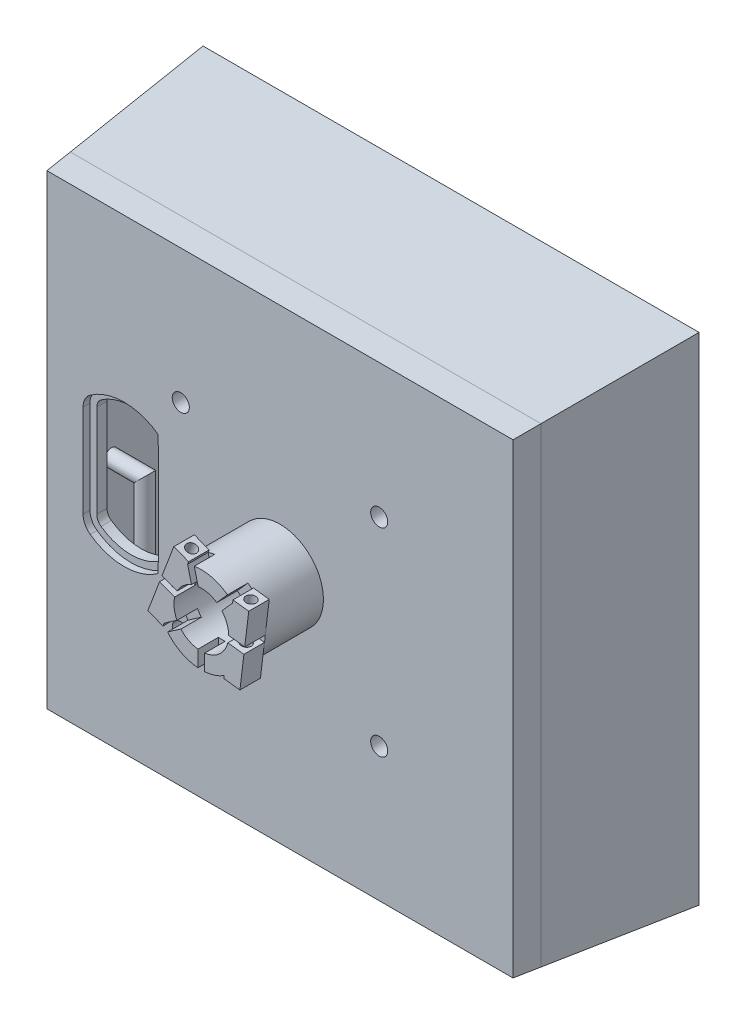
SolidWorks part; units mm, degrees
ref_plane "Front Plane" through (0, 0, 0) normal (1, 0, 0) x (0, 1, 0)
ref_plane "Top Plane" through (0, 0, 0) normal (0, 0, 1) x (0, 1, 0)
ref_plane "Right Plane" through (0, 0, 0) normal (0, 1, 0) x (-1, 0, 0)
sketch "Sketch1" plane through (0, 0, 0) normal (0, 0, 1) x (0, 1, 0)
  line L1 (0, 0) -> (100, 0)
  line L2 (0, 0) -> (0, -100)
  line L3 (0, -100) -> (100, -100)
  line L4 (100, 0) -> (100, -100)
  dimension "D1" = 100
  dimension "D2" = 100
sketch "Sketch11" plane through (0, 0, 0) normal (0, 0, 1) x (0, 1, 0)
  line L1 (0, 0) -> (145, 0)
  line L2 (0, 0) -> (0, -145)
  line L3 (0, -145) -> (145, -145)
  line L4 (145, 0) -> (145, -145)
  dimension "D1" = 145
extrude "Boss-Extrude5" add sketch "Sketch11" along normal blind 50
chamfer "Chamfer1" distance 50 angle 5 4 edges at (0, 72.5, 50) (72.5, 145, 50) (145, 72.5, 50) (72.5, 0, 50) first distance on face at (0, 72.5, 25) first distance on face at (72.5, 145, 25) first distance on face at (145, 72.5, 25) first distance on face at (72.5, 0, 25)
shell "Shell1" thickness 5
sketch "Sketch3" plane through (0, 0, 50) normal (0, 0, 1) x (1, 0, 0)
  line L0 (17.5, 72.5) -> (127.5, 72.5) construction
  line L1 (43.94, 36.94) -> (101.06, 36.94) construction
  line L2 (36.94, 43.94) -> (36.94, 101.06) construction
  line L3 (43.94, 108.06) -> (101.06, 108.06) construction
  line L4 (108.06, 43.94) -> (108.06, 101.06) construction
  line L5 (36.94, 36.94) -> (108.06, 108.06) construction
  line L6 (36.94, 108.06) -> (108.06, 36.94) construction
  line L9 (72.5, 7.5) -> (72.5, 92.5) construction
  line L12 (140.6256, 140.6256) -> (4.3744, 140.6256) construction
  line L13 (4.3744, 140.6256) -> (4.3744, 4.3744) construction
  circle A0 centre (72.5, 72.5) radius 12.7
  circle A1 centre (43.5, 101.5) radius 2.5
  circle A2 centre (101.5, 43.5) radius 2.5
  circle A3 centre (101.5, 101.5) radius 2.5
  circle A4 centre (43.5, 43.5) radius 2.5
  arc A5 (43.94, 36.94) -> (36.94, 43.94) centre (43.94, 43.94) cw construction
  arc A6 (101.06, 36.94) -> (108.06, 43.94) centre (101.06, 43.94) ccw construction
  arc A7 (108.06, 101.06) -> (101.06, 108.06) centre (101.06, 101.06) ccw construction
  arc A8 (43.94, 108.06) -> (36.94, 101.06) centre (43.94, 101.06) ccw construction
  point P17 (72.5, 140.6256)
  point P22 (4.3744, 72.5)
  point P30 (72.5, 72.5)
  dimension "D1" = 25.4
  dimension "D3" = 5
  dimension "D5" = 7
  dimension "D2" = 71.12
  dimension "D4" = 58
extrude "Cut-Extrude3" cut sketch "Sketch3" against normal up to surface (5 mm away) up to face at (72.5, 72.5, 45)
sketch "Sketch5" plane through (0, 0, 45) normal (0, 0, -1) x (1, 0, 0)
  circle A2 centre (72.5, -72.5) radius 12.7
  circle A3 centre (72.5, -72.5) radius 8
  circle A4 centre (72.5, -72.5) radius 12.7 construction
  dimension "D1" = 16
extrude "Boss-Extrude6" add sketch "Sketch5" against normal blind 28
sketch "Sketch12" plane through (0, 0, 73) normal (0, 0, 1) x (1, 0, 0)
  line L1 (58.8041, 72.6436) -> (60, 60) construction
  line L2 (60, 60) -> (60.7967, 72.675) construction
  arc A0 (31.0257, 37.6808) -> (31.2752, 37.6216) centre (31.2752, 38.1766) ccw
  arc A1 (31.0257, 37.6808) -> (30.5229, 38.269) centre (31.4752, 38.5741) cw
  arc A2 (30.5229, 38.269) -> (30.3584, 38.3716) centre (30.38, 38.2232) ccw
  arc A3 (30.3584, 38.3716) -> (30.2795, 38.3596) centre (31.2752, 32.073) ccw
  arc A4 (32.1919, 38.3716) -> (32.2709, 38.3596) centre (31.2752, 32.073) cw
  arc A5 (32.0275, 38.269) -> (32.1919, 38.3716) centre (32.1703, 38.2232) cw
  arc A6 (31.5246, 37.6808) -> (32.0275, 38.269) centre (31.0752, 38.5741) ccw
  arc A7 (31.5246, 37.6808) -> (31.2752, 37.6216) centre (31.2752, 38.1766) cw
  arc A8 (59.3046, 72.2263) -> (59.8122, 71.9146) centre (59.8034, 72.4695) ccw
  arc A9 (59.3046, 72.2263) -> (59.2119, 72.5345) centre (60.2034, 72.6645) cw
  arc A10 (59.2119, 72.5345) -> (59.052, 72.6646) centre (59.0632, 72.515) ccw
  arc A11 (59.052, 72.6646) -> (58.8041, 72.6436) centre (60, 60) ccw
  arc A12 (60.5483, 72.6882) -> (60.7967, 72.675) centre (60, 60) cw
  arc A13 (60.3926, 72.5531) -> (60.5483, 72.6882) centre (60.5419, 72.5383) cw
  arc A14 (60.3097, 72.2421) -> (60.3926, 72.5531) centre (59.3975, 72.6518) ccw
  arc A15 (60.3097, 72.2421) -> (59.8122, 71.9146) centre (59.8034, 72.4695) cw
  arc A16 (61.2257, 72.1846) -> (61.6783, 71.7973) centre (61.7565, 72.3467) ccw
  circle A17 centre (60, 60) radius 12.7 construction
  arc A18 (61.2257, 72.1846) -> (61.1824, 72.5035) centre (62.1821, 72.4768) cw
  arc A19 (61.1824, 72.5035) -> (61.0448, 72.6569) centre (61.0325, 72.5075) ccw
  arc A20 (61.0448, 72.6569) -> (60.7967, 72.675) centre (60, 60) ccw
  arc A21 (62.5265, 72.4462) -> (62.7697, 72.3943) centre (60, 60) cw
  arc A22 (62.3515, 72.3371) -> (62.5265, 72.4462) centre (62.4966, 72.2992) cw
  arc A23 (62.221, 72.043) -> (62.3515, 72.3371) centre (61.3841, 72.5903) ccw
  arc A24 (62.221, 72.043) -> (61.6783, 71.7973) centre (61.7565, 72.3467) cw
  arc A25 (63.1167, 71.8428) -> (63.5032, 71.3895) centre (63.6663, 71.9199) ccw
  arc A26 (63.1167, 71.8428) -> (63.1239, 72.1645) centre (64.107, 71.9818) cw
  arc A27 (63.1239, 72.1645) -> (63.012, 72.3377) centre (62.9764, 72.1919) ccw
  arc A28 (63.012, 72.3377) -> (62.7697, 72.3943) centre (60, 60) ccw
  arc A29 (64.4424, 71.8977) -> (64.6745, 71.8084) centre (60, 60) cw
  arc A30 (64.2525, 71.8174) -> (64.4424, 71.8977) centre (64.3899, 71.7572) cw
  arc A31 (64.0776, 71.5473) -> (64.2525, 71.8174) centre (63.3366, 72.2188) ccw
  arc A32 (64.0776, 71.5473) -> (63.5032, 71.3895) centre (63.6663, 71.9199) cw
  arc A33 (64.931, 71.2094) -> (65.2417, 70.7012) centre (65.4859, 71.1996) ccw
  arc A34 (64.931, 71.2094) -> (64.9884, 71.5261) centre (65.9308, 71.1918) cw
  arc A35 (64.9884, 71.5261) -> (64.9049, 71.7146) centre (64.847, 71.5762) ccw
  arc A36 (64.9049, 71.7146) -> (64.6745, 71.8084) centre (60, 60) ccw
  arc A37 (66.2489, 71.0563) -> (66.4642, 70.9318) centre (60, 60) cw
  arc A38 (66.0488, 71.0067) -> (66.2489, 71.0563) centre (66.1751, 70.9257) cw
  arc A39 (65.8338, 70.7672) -> (66.0488, 71.0067) centre (65.2069, 71.5464) ccw
  arc A40 (65.8338, 70.7672) -> (65.2417, 70.7012) centre (65.4859, 71.1996) cw
  arc A41 (66.6238, 70.3001) -> (66.8513, 69.7495) centre (67.1704, 70.2036) ccw
  arc A42 (66.6238, 70.3001) -> (66.73, 70.6038) centre (67.6086, 70.1262) cw
  arc A43 (66.73, 70.6038) -> (66.6771, 70.8031) centre (66.5982, 70.6755) ccw
  arc A44 (66.6771, 70.8031) -> (66.4642, 70.9318) centre (60, 60) ccw
  arc A45 (67.9015, 69.9426) -> (68.0947, 69.786) centre (60, 60) cw
  arc A46 (67.6961, 69.9249) -> (67.9015, 69.9426) centre (67.8082, 69.8252) cw
  arc A47 (67.4463, 69.7221) -> (67.6961, 69.9249) centre (66.9491, 70.5897) ccw
  arc A48 (67.4463, 69.7221) -> (66.8513, 69.7495) centre (67.1704, 70.2036) cw
  arc A49 (68.1535, 69.1371) -> (68.2921, 68.5577) centre (68.6783, 68.9563) ccw
  arc A50 (68.1535, 69.1371) -> (68.306, 69.4205) centre (69.099, 68.8113) cw
  arc A51 (68.306, 69.4205) -> (68.2849, 69.6255) centre (68.187, 69.5119) ccw
  arc A52 (68.2849, 69.6255) -> (68.0947, 69.786) centre (60, 60) ccw
  arc A53 (69.3596, 68.5841) -> (69.5259, 68.3992) centre (60, 60) cw
  arc A54 (69.154, 68.5988) -> (69.3596, 68.5841) centre (69.2491, 68.4828) cw
  arc A55 (68.8755, 68.4375) -> (69.154, 68.5988) centre (68.5201, 69.3722) ccw
  arc A56 (68.8755, 68.4375) -> (68.2921, 68.5577) centre (68.6783, 68.9563) cw
  arc A57 (69.4825, 67.7491) -> (69.5287, 67.1552) centre (69.9725, 67.4884) ccw
  arc A58 (69.4825, 67.7491) -> (69.6774, 68.0052) centre (70.3654, 67.2794) cw
  arc A59 (69.6774, 68.0052) -> (69.6886, 68.211) centre (69.5742, 68.114) ccw
  arc A60 (69.6886, 68.211) -> (69.5259, 68.3992) centre (60, 60) ccw
  arc A61 (70.5872, 67.0143) -> (70.7226, 66.8056) centre (60, 60) cw
  arc A62 (70.3864, 67.0609) -> (70.5872, 67.0143) centre (70.4622, 66.9314) cw
  arc A63 (70.0862, 66.9452) -> (70.3864, 67.0609) centre (69.8814, 67.924) ccw
  arc A64 (70.0862, 66.9452) -> (69.5287, 67.1552) centre (69.9725, 67.4884) cw
  arc A65 (70.578, 66.1703) -> (70.5307, 65.5765) centre (71.0212, 65.8362) ccw
  arc A66 (70.578, 66.1703) -> (70.8105, 66.3927) centre (71.3765, 65.5683) cw
  arc A67 (70.8105, 66.3927) -> (70.8538, 66.5943) centre (70.7256, 66.5164) ccw
  arc A68 (70.8538, 66.5943) -> (70.7226, 66.8056) centre (60, 60) ccw
  arc A69 (71.5542, 65.2717) -> (71.6552, 65.0444) centre (60, 60) cw
  arc A70 (71.3631, 65.3492) -> (71.5542, 65.2717) centre (71.4177, 65.2095) cw
  arc A71 (71.0484, 65.2819) -> (71.3631, 65.3492) centre (70.9993, 66.2806) ccw
  arc A72 (71.0484, 65.2819) -> (70.5307, 65.5765) centre (71.0212, 65.8362) cw
  arc A73 (71.413, 64.4395) -> (71.2734, 63.8604) centre (71.7985, 64.0402) ccw
  arc A74 (71.413, 64.4395) -> (71.6775, 64.6229) centre (72.1075, 63.7201) cw
  arc A75 (71.6775, 64.6229) -> (71.7518, 64.8152) centre (71.613, 64.7583) ccw
  arc A76 (71.7518, 64.8152) -> (71.6552, 65.0444) centre (60, 60) ccw
  arc A77 (72.2366, 63.3994) -> (72.3008, 63.159) centre (60, 60) cw
  arc A78 (72.06, 63.5057) -> (72.2366, 63.3994) centre (72.0921, 63.3592) cw
  arc A79 (71.7387, 63.4885) -> (72.06, 63.5057) centre (71.8464, 64.4826) ccw
  arc A80 (71.7387, 63.4885) -> (71.2734, 63.8604) centre (71.7985, 64.0402) cw
  arc A81 (71.967, 62.5995) -> (71.7385, 62.0494) centre (72.2852, 62.1448) ccw
  arc A82 (71.967, 62.5995) -> (72.2569, 62.7392) centre (72.5404, 61.7802) cw
  arc A83 (72.2569, 62.7392) -> (72.3603, 62.9175) centre (72.2144, 62.8831) ccw
  arc A84 (72.3603, 62.9175) -> (72.3008, 63.159) centre (60, 60) ccw
  arc A85 (72.6177, 61.4433) -> (72.6436, 61.1959) centre (60, 60) cw
  arc A86 (72.46, 61.576) -> (72.6177, 61.4433) centre (72.4687, 61.4262) cw
  arc A87 (72.1399, 61.6092) -> (72.46, 61.576) centre (72.4018, 62.5743) ccw
  arc A88 (72.1399, 61.6092) -> (71.7385, 62.0494) centre (72.2852, 62.1448) cw
  arc A89 (72.2263, 60.6954) -> (71.9146, 60.1878) centre (72.4695, 60.1966) ccw
  arc A90 (72.2263, 60.6954) -> (72.5345, 60.7881) centre (72.6645, 59.7966) cw
  arc A91 (72.5345, 60.7881) -> (72.6646, 60.948) centre (72.515, 60.9368) ccw
  arc A92 (72.6646, 60.948) -> (72.6436, 61.1959) centre (60, 60) ccw
  arc A93 (72.6882, 59.4517) -> (72.675, 59.2033) centre (60, 60) cw
  arc A94 (72.5531, 59.6074) -> (72.6882, 59.4517) centre (72.5383, 59.4581) cw
  arc A95 (72.2421, 59.6903) -> (72.5531, 59.6074) centre (72.6518, 60.6025) ccw
  arc A96 (72.2421, 59.6903) -> (71.9146, 60.1878) centre (72.4695, 60.1966) cw
  arc A97 (72.1846, 58.7743) -> (71.7973, 58.3217) centre (72.3467, 58.2435) ccw
  arc A98 (72.1846, 58.7743) -> (72.5035, 58.8176) centre (72.4768, 57.8179) cw
  arc A99 (72.5035, 58.8176) -> (72.6569, 58.9552) centre (72.5075, 58.9675) ccw
  arc A100 (72.6569, 58.9552) -> (72.675, 59.2033) centre (60, 60) ccw
  arc A101 (72.4462, 57.4735) -> (72.3943, 57.2303) centre (60, 60) cw
  arc A102 (72.3371, 57.6485) -> (72.4462, 57.4735) centre (72.2992, 57.5034) cw
  arc A103 (72.043, 57.779) -> (72.3371, 57.6485) centre (72.5903, 58.6159) ccw
  arc A104 (72.043, 57.779) -> (71.7973, 58.3217) centre (72.3467, 58.2435) cw
  arc A105 (71.8428, 56.8833) -> (71.3895, 56.4968) centre (71.9199, 56.3337) ccw
  arc A106 (71.8428, 56.8833) -> (72.1645, 56.8761) centre (71.9818, 55.893) cw
  arc A107 (72.1645, 56.8761) -> (72.3377, 56.988) centre (72.1919, 57.0236) ccw
  arc A108 (72.3377, 56.988) -> (72.3943, 57.2303) centre (60, 60) ccw
  arc A109 (71.8977, 55.5576) -> (71.8084, 55.3255) centre (60, 60) cw
  arc A110 (71.8174, 55.7475) -> (71.8977, 55.5576) centre (71.7572, 55.6101) cw
  arc A111 (71.5473, 55.9224) -> (71.8174, 55.7475) centre (72.2188, 56.6634) ccw
  arc A112 (71.5473, 55.9224) -> (71.3895, 56.4968) centre (71.9199, 56.3337) cw
  arc A113 (71.2094, 55.069) -> (70.7012, 54.7583) centre (71.1996, 54.5141) ccw
  arc A114 (71.2094, 55.069) -> (71.5261, 55.0116) centre (71.1918, 54.0692) cw
  arc A115 (71.5261, 55.0116) -> (71.7146, 55.0951) centre (71.5762, 55.153) ccw
  arc A116 (71.7146, 55.0951) -> (71.8084, 55.3255) centre (60, 60) ccw
  arc A117 (71.0563, 53.7511) -> (70.9318, 53.5358) centre (60, 60) cw
  arc A118 (71.0067, 53.9512) -> (71.0563, 53.7511) centre (70.9257, 53.8249) cw
  arc A119 (70.7672, 54.1662) -> (71.0067, 53.9512) centre (71.5464, 54.7931) ccw
  arc A120 (70.7672, 54.1662) -> (70.7012, 54.7583) centre (71.1996, 54.5141) cw
  arc A121 (70.3001, 53.3762) -> (69.7495, 53.1487) centre (70.2036, 52.8296) ccw
  arc A122 (70.3001, 53.3762) -> (70.6038, 53.27) centre (70.1262, 52.3914) cw
  arc A123 (70.6038, 53.27) -> (70.8031, 53.3229) centre (70.6755, 53.4018) ccw
  arc A124 (70.8031, 53.3229) -> (70.9318, 53.5358) centre (60, 60) ccw
  arc A125 (69.9426, 52.0985) -> (69.786, 51.9053) centre (60, 60) cw
  arc A126 (69.9249, 52.3039) -> (69.9426, 52.0985) centre (69.8252, 52.1918) cw
  arc A127 (69.7221, 52.5537) -> (69.9249, 52.3039) centre (70.5897, 53.0509) ccw
  arc A128 (69.7221, 52.5537) -> (69.7495, 53.1487) centre (70.2036, 52.8296) cw
  arc A129 (69.1371, 51.8465) -> (68.5577, 51.7079) centre (68.9563, 51.3217) ccw
  arc A130 (69.1371, 51.8465) -> (69.4205, 51.694) centre (68.8113, 50.901) cw
  arc A131 (69.4205, 51.694) -> (69.6255, 51.7151) centre (69.5119, 51.813) ccw
  arc A132 (69.6255, 51.7151) -> (69.786, 51.9053) centre (60, 60) ccw
  arc A133 (68.5841, 50.6404) -> (68.3992, 50.4741) centre (60, 60) cw
  arc A134 (68.5988, 50.846) -> (68.5841, 50.6404) centre (68.4828, 50.7509) cw
  arc A135 (68.4375, 51.1245) -> (68.5988, 50.846) centre (69.3722, 51.4799) ccw
  arc A136 (68.4375, 51.1245) -> (68.5577, 51.7079) centre (68.9563, 51.3217) cw
  arc A137 (67.7491, 50.5175) -> (67.1552, 50.4713) centre (67.4884, 50.0275) ccw
  arc A138 (67.7491, 50.5175) -> (68.0052, 50.3226) centre (67.2794, 49.6346) cw
  arc A139 (68.0052, 50.3226) -> (68.211, 50.3114) centre (68.114, 50.4258) ccw
  arc A140 (68.211, 50.3114) -> (68.3992, 50.4741) centre (60, 60) ccw
  arc A141 (67.0143, 49.4128) -> (66.8056, 49.2774) centre (60, 60) cw
  arc A142 (67.0609, 49.6136) -> (67.0143, 49.4128) centre (66.9314, 49.5378) cw
  arc A143 (66.9452, 49.9138) -> (67.0609, 49.6136) centre (67.924, 50.1186) ccw
  arc A144 (66.9452, 49.9138) -> (67.1552, 50.4713) centre (67.4884, 50.0275) cw
  arc A145 (66.1703, 49.422) -> (65.5765, 49.4693) centre (65.8362, 48.9788) ccw
  arc A146 (66.1703, 49.422) -> (66.3927, 49.1895) centre (65.5683, 48.6235) cw
  arc A147 (66.3927, 49.1895) -> (66.5943, 49.1462) centre (66.5164, 49.2744) ccw
  arc A148 (66.5943, 49.1462) -> (66.8056, 49.2774) centre (60, 60) ccw
  arc A149 (65.2717, 48.4458) -> (65.0444, 48.3448) centre (60, 60) cw
  arc A150 (65.3492, 48.6369) -> (65.2717, 48.4458) centre (65.2095, 48.5823) cw
  arc A151 (65.2819, 48.9516) -> (65.3492, 48.6369) centre (66.2806, 49.0007) ccw
  arc A152 (65.2819, 48.9516) -> (65.5765, 49.4693) centre (65.8362, 48.9788) cw
  arc A153 (64.4395, 48.587) -> (63.8604, 48.7266) centre (64.0402, 48.2015) ccw
  arc A154 (64.4395, 48.587) -> (64.6229, 48.3225) centre (63.7201, 47.8925) cw
  arc A155 (64.6229, 48.3225) -> (64.8152, 48.2482) centre (64.7583, 48.387) ccw
  arc A156 (64.8152, 48.2482) -> (65.0444, 48.3448) centre (60, 60) ccw
  arc A157 (63.3994, 47.7634) -> (63.159, 47.6992) centre (60, 60) cw
  arc A158 (63.5057, 47.94) -> (63.3994, 47.7634) centre (63.3592, 47.9079) cw
  arc A159 (63.4885, 48.2613) -> (63.5057, 47.94) centre (64.4826, 48.1536) ccw
  arc A160 (63.4885, 48.2613) -> (63.8604, 48.7266) centre (64.0402, 48.2015) cw
  arc A161 (62.5995, 48.033) -> (62.0494, 48.2615) centre (62.1448, 47.7148) ccw
  arc A162 (62.5995, 48.033) -> (62.7392, 47.7431) centre (61.7802, 47.4596) cw
  arc A163 (62.7392, 47.7431) -> (62.9175, 47.6397) centre (62.8831, 47.7856) ccw
  arc A164 (62.9175, 47.6397) -> (63.159, 47.6992) centre (60, 60) ccw
  arc A165 (61.4433, 47.3823) -> (61.1959, 47.3564) centre (60, 60) cw
  arc A166 (61.576, 47.54) -> (61.4433, 47.3823) centre (61.4262, 47.5313) cw
  arc A167 (61.6092, 47.8601) -> (61.576, 47.54) centre (62.5743, 47.5982) ccw
  arc A168 (61.6092, 47.8601) -> (62.0494, 48.2615) centre (62.1448, 47.7148) cw
  arc A169 (60.6954, 47.7737) -> (60.1878, 48.0854) centre (60.1966, 47.5305) ccw
  arc A170 (60.6954, 47.7737) -> (60.7881, 47.4655) centre (59.7966, 47.3355) cw
  arc A171 (60.7881, 47.4655) -> (60.948, 47.3354) centre (60.9368, 47.485) ccw
  arc A172 (60.948, 47.3354) -> (61.1959, 47.3564) centre (60, 60) ccw
  arc A173 (59.4517, 47.3118) -> (59.2033, 47.325) centre (60, 60) cw
  arc A174 (59.6074, 47.4469) -> (59.4517, 47.3118) centre (59.4581, 47.4617) cw
  arc A175 (59.6903, 47.7579) -> (59.6074, 47.4469) centre (60.6025, 47.3482) ccw
  arc A176 (59.6903, 47.7579) -> (60.1878, 48.0854) centre (60.1966, 47.5305) cw
  arc A177 (58.7743, 47.8154) -> (58.3217, 48.2027) centre (58.2435, 47.6533) ccw
  arc A178 (58.7743, 47.8154) -> (58.8176, 47.4965) centre (57.8179, 47.5232) cw
  arc A179 (58.8176, 47.4965) -> (58.9552, 47.3431) centre (58.9675, 47.4925) ccw
  arc A180 (58.9552, 47.3431) -> (59.2033, 47.325) centre (60, 60) ccw
  arc A181 (57.4735, 47.5538) -> (57.2303, 47.6057) centre (60, 60) cw
  arc A182 (57.6485, 47.6629) -> (57.4735, 47.5538) centre (57.5034, 47.7008) cw
  arc A183 (57.779, 47.957) -> (57.6485, 47.6629) centre (58.6159, 47.4097) ccw
  arc A184 (57.779, 47.957) -> (58.3217, 48.2027) centre (58.2435, 47.6533) cw
  arc A185 (56.8833, 48.1572) -> (56.4968, 48.6105) centre (56.3337, 48.0801) ccw
  arc A186 (56.8833, 48.1572) -> (56.8761, 47.8355) centre (55.893, 48.0182) cw
  arc A187 (56.8761, 47.8355) -> (56.988, 47.6623) centre (57.0236, 47.8081) ccw
  arc A188 (56.988, 47.6623) -> (57.2303, 47.6057) centre (60, 60) ccw
  arc A189 (55.5576, 48.1023) -> (55.3255, 48.1916) centre (60, 60) cw
  arc A190 (55.7475, 48.1826) -> (55.5576, 48.1023) centre (55.6101, 48.2428) cw
  arc A191 (55.9224, 48.4527) -> (55.7475, 48.1826) centre (56.6634, 47.7812) ccw
  arc A192 (55.9224, 48.4527) -> (56.4968, 48.6105) centre (56.3337, 48.0801) cw
  arc A193 (55.069, 48.7906) -> (54.7583, 49.2988) centre (54.5141, 48.8004) ccw
  arc A194 (55.069, 48.7906) -> (55.0116, 48.4739) centre (54.0692, 48.8082) cw
  arc A195 (55.0116, 48.4739) -> (55.0951, 48.2854) centre (55.153, 48.4238) ccw
  arc A196 (55.0951, 48.2854) -> (55.3255, 48.1916) centre (60, 60) ccw
  arc A197 (53.7511, 48.9437) -> (53.5358, 49.0682) centre (60, 60) cw
  arc A198 (53.9512, 48.9933) -> (53.7511, 48.9437) centre (53.8249, 49.0743) cw
  arc A199 (54.1662, 49.2328) -> (53.9512, 48.9933) centre (54.7931, 48.4536) ccw
  arc A200 (54.1662, 49.2328) -> (54.7583, 49.2988) centre (54.5141, 48.8004) cw
  arc A201 (53.3762, 49.6999) -> (53.1487, 50.2505) centre (52.8296, 49.7964) ccw
  arc A202 (53.3762, 49.6999) -> (53.27, 49.3962) centre (52.3914, 49.8738) cw
  arc A203 (53.27, 49.3962) -> (53.3229, 49.1969) centre (53.4018, 49.3245) ccw
  arc A204 (53.3229, 49.1969) -> (53.5358, 49.0682) centre (60, 60) ccw
  arc A205 (52.0985, 50.0574) -> (51.9053, 50.214) centre (60, 60) cw
  arc A206 (52.3039, 50.0751) -> (52.0985, 50.0574) centre (52.1918, 50.1748) cw
  arc A207 (52.5537, 50.2779) -> (52.3039, 50.0751) centre (53.0509, 49.4103) ccw
  arc A208 (52.5537, 50.2779) -> (53.1487, 50.2505) centre (52.8296, 49.7964) cw
  arc A209 (51.8465, 50.8629) -> (51.7079, 51.4423) centre (51.3217, 51.0437) ccw
  arc A210 (51.8465, 50.8629) -> (51.694, 50.5795) centre (50.901, 51.1887) cw
  arc A211 (51.694, 50.5795) -> (51.7151, 50.3745) centre (51.813, 50.4881) ccw
  arc A212 (51.7151, 50.3745) -> (51.9053, 50.214) centre (60, 60) ccw
  arc A213 (50.6404, 51.4159) -> (50.4741, 51.6008) centre (60, 60) cw
  arc A214 (50.846, 51.4012) -> (50.6404, 51.4159) centre (50.7509, 51.5172) cw
  arc A215 (51.1245, 51.5625) -> (50.846, 51.4012) centre (51.4799, 50.6278) ccw
  arc A216 (51.1245, 51.5625) -> (51.7079, 51.4423) centre (51.3217, 51.0437) cw
  arc A217 (50.5175, 52.2509) -> (50.4713, 52.8448) centre (50.0275, 52.5116) ccw
  arc A218 (50.5175, 52.2509) -> (50.3226, 51.9948) centre (49.6346, 52.7206) cw
  arc A219 (50.3226, 51.9948) -> (50.3114, 51.789) centre (50.4258, 51.886) ccw
  arc A220 (50.3114, 51.789) -> (50.4741, 51.6008) centre (60, 60) ccw
  arc A221 (49.4128, 52.9857) -> (49.2774, 53.1944) centre (60, 60) cw
  arc A222 (49.6136, 52.9391) -> (49.4128, 52.9857) centre (49.5378, 53.0686) cw
  arc A223 (49.9138, 53.0548) -> (49.6136, 52.9391) centre (50.1186, 52.076) ccw
  arc A224 (49.9138, 53.0548) -> (50.4713, 52.8448) centre (50.0275, 52.5116) cw
  arc A225 (49.422, 53.8297) -> (49.4693, 54.4235) centre (48.9788, 54.1638) ccw
  arc A226 (49.422, 53.8297) -> (49.1895, 53.6073) centre (48.6235, 54.4317) cw
  arc A227 (49.1895, 53.6073) -> (49.1462, 53.4057) centre (49.2744, 53.4836) ccw
  arc A228 (49.1462, 53.4057) -> (49.2774, 53.1944) centre (60, 60) ccw
  arc A229 (48.4458, 54.7283) -> (48.3448, 54.9556) centre (60, 60) cw
  arc A230 (48.6369, 54.6508) -> (48.4458, 54.7283) centre (48.5823, 54.7905) cw
  arc A231 (48.9516, 54.7181) -> (48.6369, 54.6508) centre (49.0007, 53.7194) ccw
  arc A232 (48.9516, 54.7181) -> (49.4693, 54.4235) centre (48.9788, 54.1638) cw
  arc A233 (48.587, 55.5605) -> (48.7266, 56.1396) centre (48.2015, 55.9598) ccw
  arc A234 (48.587, 55.5605) -> (48.3225, 55.3771) centre (47.8925, 56.2799) cw
  arc A235 (48.3225, 55.3771) -> (48.2482, 55.1848) centre (48.387, 55.2417) ccw
  arc A236 (48.2482, 55.1848) -> (48.3448, 54.9556) centre (60, 60) ccw
  arc A237 (47.7634, 56.6006) -> (47.6992, 56.841) centre (60, 60) cw
  arc A238 (47.94, 56.4943) -> (47.7634, 56.6006) centre (47.9079, 56.6408) cw
  arc A239 (48.2613, 56.5115) -> (47.94, 56.4943) centre (48.1536, 55.5174) ccw
  arc A240 (48.2613, 56.5115) -> (48.7266, 56.1396) centre (48.2015, 55.9598) cw
  arc A241 (48.033, 57.4005) -> (48.2615, 57.9506) centre (47.7148, 57.8552) ccw
  arc A242 (48.033, 57.4005) -> (47.7431, 57.2608) centre (47.4596, 58.2198) cw
  arc A243 (47.7431, 57.2608) -> (47.6397, 57.0825) centre (47.7856, 57.1169) ccw
  arc A244 (47.6397, 57.0825) -> (47.6992, 56.841) centre (60, 60) ccw
  arc A245 (47.3823, 58.5567) -> (47.3564, 58.8041) centre (60, 60) cw
  arc A246 (47.54, 58.424) -> (47.3823, 58.5567) centre (47.5313, 58.5738) cw
  arc A247 (47.8601, 58.3908) -> (47.54, 58.424) centre (47.5982, 57.4257) ccw
  arc A248 (47.8601, 58.3908) -> (48.2615, 57.9506) centre (47.7148, 57.8552) cw
  arc A249 (47.7737, 59.3046) -> (48.0854, 59.8122) centre (47.5305, 59.8034) ccw
  arc A250 (47.7737, 59.3046) -> (47.4655, 59.2119) centre (47.3355, 60.2034) cw
  arc A251 (47.4655, 59.2119) -> (47.3354, 59.052) centre (47.485, 59.0632) ccw
  arc A252 (47.3354, 59.052) -> (47.3564, 58.8041) centre (60, 60) ccw
  arc A253 (47.3118, 60.5483) -> (47.325, 60.7967) centre (60, 60) cw
  arc A254 (47.4469, 60.3926) -> (47.3118, 60.5483) centre (47.4617, 60.5419) cw
  arc A255 (47.7579, 60.3097) -> (47.4469, 60.3926) centre (47.3482, 59.3975) ccw
  arc A256 (47.7579, 60.3097) -> (48.0854, 59.8122) centre (47.5305, 59.8034) cw
  arc A257 (47.8154, 61.2257) -> (48.2027, 61.6783) centre (47.6533, 61.7565) ccw
  arc A258 (47.8154, 61.2257) -> (47.4965, 61.1824) centre (47.5232, 62.1821) cw
  arc A259 (47.4965, 61.1824) -> (47.3431, 61.0448) centre (47.4925, 61.0325) ccw
  arc A260 (47.3431, 61.0448) -> (47.325, 60.7967) centre (60, 60) ccw
  arc A261 (47.5538, 62.5265) -> (47.6057, 62.7697) centre (60, 60) cw
  arc A262 (47.6629, 62.3515) -> (47.5538, 62.5265) centre (47.7008, 62.4966) cw
  arc A263 (47.957, 62.221) -> (47.6629, 62.3515) centre (47.4097, 61.3841) ccw
  arc A264 (47.957, 62.221) -> (48.2027, 61.6783) centre (47.6533, 61.7565) cw
  arc A265 (48.1572, 63.1167) -> (48.6105, 63.5032) centre (48.0801, 63.6663) ccw
  arc A266 (48.1572, 63.1167) -> (47.8355, 63.1239) centre (48.0182, 64.107) cw
  arc A267 (47.8355, 63.1239) -> (47.6623, 63.012) centre (47.8081, 62.9764) ccw
  arc A268 (47.6623, 63.012) -> (47.6057, 62.7697) centre (60, 60) ccw
  arc A269 (48.1023, 64.4424) -> (48.1916, 64.6745) centre (60, 60) cw
  arc A270 (48.1826, 64.2525) -> (48.1023, 64.4424) centre (48.2428, 64.3899) cw
  arc A271 (48.4527, 64.0776) -> (48.1826, 64.2525) centre (47.7812, 63.3366) ccw
  arc A272 (48.4527, 64.0776) -> (48.6105, 63.5032) centre (48.0801, 63.6663) cw
  arc A273 (48.7906, 64.931) -> (49.2988, 65.2417) centre (48.8004, 65.4859) ccw
  arc A274 (48.7906, 64.931) -> (48.4739, 64.9884) centre (48.8082, 65.9308) cw
  arc A275 (48.4739, 64.9884) -> (48.2854, 64.9049) centre (48.4238, 64.847) ccw
  arc A276 (48.2854, 64.9049) -> (48.1916, 64.6745) centre (60, 60) ccw
  arc A277 (48.9437, 66.2489) -> (49.0682, 66.4642) centre (60, 60) cw
  arc A278 (48.9933, 66.0488) -> (48.9437, 66.2489) centre (49.0743, 66.1751) cw
  arc A279 (49.2328, 65.8338) -> (48.9933, 66.0488) centre (48.4536, 65.2069) ccw
  arc A280 (49.2328, 65.8338) -> (49.2988, 65.2417) centre (48.8004, 65.4859) cw
  arc A281 (49.6999, 66.6238) -> (50.2505, 66.8513) centre (49.7964, 67.1704) ccw
  arc A282 (49.6999, 66.6238) -> (49.3962, 66.73) centre (49.8738, 67.6086) cw
  arc A283 (49.3962, 66.73) -> (49.1969, 66.6771) centre (49.3245, 66.5982) ccw
  arc A284 (49.1969, 66.6771) -> (49.0682, 66.4642) centre (60, 60) ccw
  arc A285 (50.0574, 67.9015) -> (50.214, 68.0947) centre (60, 60) cw
  arc A286 (50.0751, 67.6961) -> (50.0574, 67.9015) centre (50.1748, 67.8082) cw
  arc A287 (50.2779, 67.4463) -> (50.0751, 67.6961) centre (49.4103, 66.9491) ccw
  arc A288 (50.2779, 67.4463) -> (50.2505, 66.8513) centre (49.7964, 67.1704) cw
  arc A289 (50.8629, 68.1535) -> (51.4423, 68.2921) centre (51.0437, 68.6783) ccw
  arc A290 (50.8629, 68.1535) -> (50.5795, 68.306) centre (51.1887, 69.099) cw
  arc A291 (50.5795, 68.306) -> (50.3745, 68.2849) centre (50.4881, 68.187) ccw
  arc A292 (50.3745, 68.2849) -> (50.214, 68.0947) centre (60, 60) ccw
  arc A293 (51.4159, 69.3596) -> (51.6008, 69.5259) centre (60, 60) cw
  arc A294 (51.4012, 69.154) -> (51.4159, 69.3596) centre (51.5172, 69.2491) cw
  arc A295 (51.5625, 68.8755) -> (51.4012, 69.154) centre (50.6278, 68.5201) ccw
  arc A296 (51.5625, 68.8755) -> (51.4423, 68.2921) centre (51.0437, 68.6783) cw
  arc A297 (52.2509, 69.4825) -> (52.8448, 69.5287) centre (52.5116, 69.9725) ccw
  arc A298 (52.2509, 69.4825) -> (51.9948, 69.6774) centre (52.7206, 70.3654) cw
  arc A299 (51.9948, 69.6774) -> (51.789, 69.6886) centre (51.886, 69.5742) ccw
  arc A300 (51.789, 69.6886) -> (51.6008, 69.5259) centre (60, 60) ccw
  arc A301 (52.9857, 70.5872) -> (53.1944, 70.7226) centre (60, 60) cw
  arc A302 (52.9391, 70.3864) -> (52.9857, 70.5872) centre (53.0686, 70.4622) cw
  arc A303 (53.0548, 70.0862) -> (52.9391, 70.3864) centre (52.076, 69.8814) ccw
  arc A304 (53.0548, 70.0862) -> (52.8448, 69.5287) centre (52.5116, 69.9725) cw
  arc A305 (53.8297, 70.578) -> (54.4235, 70.5307) centre (54.1638, 71.0212) ccw
  arc A306 (53.8297, 70.578) -> (53.6073, 70.8105) centre (54.4317, 71.3765) cw
  arc A307 (53.6073, 70.8105) -> (53.4057, 70.8538) centre (53.4836, 70.7256) ccw
  arc A308 (53.4057, 70.8538) -> (53.1944, 70.7226) centre (60, 60) ccw
  arc A309 (54.7283, 71.5542) -> (54.9556, 71.6552) centre (60, 60) cw
  arc A310 (54.6508, 71.3631) -> (54.7283, 71.5542) centre (54.7905, 71.4177) cw
  arc A311 (54.7181, 71.0484) -> (54.6508, 71.3631) centre (53.7194, 70.9993) ccw
  arc A312 (54.7181, 71.0484) -> (54.4235, 70.5307) centre (54.1638, 71.0212) cw
  arc A313 (55.5605, 71.413) -> (56.1396, 71.2734) centre (55.9598, 71.7985) ccw
  arc A314 (55.5605, 71.413) -> (55.3771, 71.6775) centre (56.2799, 72.1075) cw
  arc A315 (55.3771, 71.6775) -> (55.1848, 71.7518) centre (55.2417, 71.613) ccw
  arc A316 (55.1848, 71.7518) -> (54.9556, 71.6552) centre (60, 60) ccw
  arc A317 (56.6006, 72.2366) -> (56.841, 72.3008) centre (60, 60) cw
  arc A318 (56.4943, 72.06) -> (56.6006, 72.2366) centre (56.6408, 72.0921) cw
  arc A319 (56.5115, 71.7387) -> (56.4943, 72.06) centre (55.5174, 71.8464) ccw
  arc A320 (56.5115, 71.7387) -> (56.1396, 71.2734) centre (55.9598, 71.7985) cw
  arc A321 (57.4005, 71.967) -> (57.9506, 71.7385) centre (57.8552, 72.2852) ccw
  arc A322 (57.4005, 71.967) -> (57.2608, 72.2569) centre (58.2198, 72.5404) cw
  arc A323 (57.2608, 72.2569) -> (57.0825, 72.3603) centre (57.1169, 72.2144) ccw
  arc A324 (57.0825, 72.3603) -> (56.841, 72.3008) centre (60, 60) ccw
  arc A325 (58.5567, 72.6177) -> (58.8041, 72.6436) centre (60, 60) cw
  arc A326 (58.424, 72.46) -> (58.5567, 72.6177) centre (58.5738, 72.4687) cw
  arc A327 (58.3908, 72.1399) -> (58.424, 72.46) centre (57.4257, 72.4018) ccw
  arc A328 (58.3908, 72.1399) -> (57.9506, 71.7385) centre (57.8552, 72.2852) cw
sketch "Sketch8" plane through (0, 0, 0) normal (0, 1, 0) x (-1, 0, 0)
  line L1 (-76.9, 5) -> (-96.9, 5)
  line L2 (-76.9, 5) -> (-76.9, 25)
  line L3 (-76.9, 25) -> (-96.9, 25)
  line L4 (-96.9, 5) -> (-96.9, 25)
  line L5 (-76.9, 5) -> (-96.9, 25) construction
  line L6 (-76.9, 25) -> (-96.9, 5) construction
  line L7 (-72.5, 50) -> (-72.5, 0) construction
  line L8 (-4.3744, 50) -> (-140.6256, 50) construction
  line L9 (0, 0) -> (-145, 0) construction
  point P1 (-86.9, 15)
  dimension "D1" = 20
  dimension "D3" = 14.4
  dimension "D2" = 20
  dimension "D4" = 5
extrude "Boss-Extrude8" add sketch "Sketch8" along normal up to surface (0.4374 mm away) up to face at (72.5, 2.1872, 25)
sketch "Sketch13" plane through (0, 0, 0) normal (0, -1, 0) x (1, 0, 0)
  line L0 (76.9, 25) -> (96.9, 5) construction
  line L1 (76.9, 5) -> (96.9, 25) construction
  circle A0 centre (86.9, 15) radius 6
  dimension "D1" = 12
extrude "Cut-Extrude4" cut sketch "Sketch13" against normal up to surface (5.8065 mm away) up to face at (72.5, 7.2063, 25)
sketch "Sketch17" plane through (0, 0, 5) normal (0, 0, 1) x (1, 0, 0)
  circle A0 centre (129.1079, 67.5) radius 1.75 construction
  circle A1 centre (128.9435, 17.7) radius 1.75 construction
  circle A2 centre (33.4435, 17.7) radius 1.75 construction
  circle A3 centre (33.6435, 67.5) radius 1.75 construction
  circle A4 centre (71.9565, 80.6012) radius 1.35 construction
  circle A5 centre (13.9565, 80.6012) radius 1.35 construction
  circle A6 centre (13.9565, 129.6012) radius 1.35 construction
  circle A7 centre (71.9565, 129.6012) radius 1.35 construction
  circle A8 centre (129.1079, 67.5) radius 1.85
  circle A9 centre (128.9435, 17.7) radius 1.85
  circle A10 centre (33.4435, 17.7) radius 1.85
  circle A11 centre (33.6435, 67.5) radius 1.85
  circle A12 centre (71.9565, 80.6012) radius 1.45
  circle A13 centre (13.9565, 80.6012) radius 1.45
  circle A14 centre (13.9565, 129.6012) radius 1.45
  circle A15 centre (71.9565, 129.6012) radius 1.45
  dimension "D1" = 0.1
extrude "Cut-Extrude5" cut sketch "Sketch17" against normal through all
sketch "Sketch18" plane through (0, 0, 0) normal (0, 0, -1) x (1, 0, 0)
  circle A0 centre (71.9565, -129.6012) radius 3.25
  circle A1 centre (13.9565, -80.6012) radius 3.25
  circle A2 centre (13.9565, -129.6012) radius 3.25
  circle A3 centre (71.9565, -80.6012) radius 3.25
  circle A4 centre (33.6435, -67.5) radius 3.25
  circle A5 centre (129.1079, -67.5) radius 3.25
  circle A6 centre (128.9435, -17.7) radius 3.25
  circle A7 centre (33.4435, -17.7) radius 3.25
  dimension "D1" = 6.5
extrude "Cut-Extrude6" cut sketch "Sketch18" against normal blind 3
sketch "Sketch19" plane through (0, 0, 5) normal (0, 0, 1) x (1, 0, 0)
  circle A0 centre (13.9565, 129.6012) radius 3.25
  circle A1 centre (71.9565, 129.6012) radius 3.25
  circle A2 centre (71.9565, 80.6012) radius 3.25
  circle A3 centre (13.9565, 80.6012) radius 3.25
  circle A4 centre (33.6435, 67.5) radius 3.25
  circle A5 centre (33.4435, 17.7) radius 3.25
  circle A6 centre (128.9435, 17.7) radius 3.25
  circle A7 centre (129.1079, 67.5) radius 3.25
  circle A8 centre (13.9565, 129.6012) radius 1.45
  circle A9 centre (71.9565, 129.6012) radius 1.5736
  circle A10 centre (71.9565, 80.6012) radius 1.45
  circle A11 centre (13.9565, 80.6012) radius 1.45
  circle A12 centre (33.6435, 67.5) radius 1.85
  circle A13 centre (33.4435, 17.7) radius 1.85
  circle A14 centre (129.1079, 67.5) radius 1.85
  circle A15 centre (128.9435, 17.7) radius 1.85
  dimension "D1" = 6.5
ref_plane "Plane1" through (0, 0, 35) normal (0, 0, 1) x (1, 0, 0)
sketch "Sketch20" plane through (0, 0, 35) normal (0, 0, 1) x (1, 0, 0)
  line L0 (72.5, 145) -> (72.5, 72.5) construction
  line L1 (145, 145) -> (0, 145) construction
  line L2 (18, 82.5) -> (5.5, 82.5)
  line L3 (0, 72.5) -> (72.5, 72.5) construction
  line L4 (0, 145) -> (0, 0) construction
  line L5 (5.5, 82.5) -> (5.5, 62.5)
  line L6 (18, 82.5) -> (18, 117)
  line L7 (28, 127) -> (62.5, 127)
  line L8 (62.5, 127) -> (62.5, 139.5)
  line L9 (62.5, 139.5) -> (82.5, 139.5)
  line L10 (28, 127) -> (15.5, 139.5)
  line L11 (15.5, 139.5) -> (5.5, 139.5)
  line L12 (5.5, 139.5) -> (5.5, 129.5)
  line L13 (5.5, 129.5) -> (18, 117)
  line L14 (5.5, 15.5) -> (18, 28)
  line L15 (5.5, 5.5) -> (5.5, 15.5)
  line L16 (15.5, 5.5) -> (5.5, 5.5)
  line L17 (28, 18) -> (15.5, 5.5)
  line L18 (62.5, 5.5) -> (82.5, 5.5)
  line L19 (62.5, 18) -> (62.5, 5.5)
  line L20 (28, 18) -> (62.5, 18)
  line L21 (18, 62.5) -> (18, 28)
  line L22 (18, 62.5) -> (5.5, 62.5)
  line L23 (127, 62.5) -> (139.5, 62.5)
  line L24 (127, 62.5) -> (127, 28)
  line L25 (117, 18) -> (82.5, 18)
  line L26 (82.5, 18) -> (82.5, 5.5)
  line L27 (117, 18) -> (129.5, 5.5)
  line L28 (129.5, 5.5) -> (139.5, 5.5)
  line L29 (139.5, 5.5) -> (139.5, 15.5)
  line L30 (139.5, 15.5) -> (127, 28)
  line L31 (139.5, 129.5) -> (127, 117)
  line L32 (139.5, 139.5) -> (139.5, 129.5)
  line L33 (129.5, 139.5) -> (139.5, 139.5)
  line L34 (117, 127) -> (129.5, 139.5)
  line L35 (82.5, 127) -> (82.5, 139.5)
  line L36 (117, 127) -> (82.5, 127)
  line L37 (127, 82.5) -> (127, 117)
  line L38 (139.5, 82.5) -> (139.5, 62.5)
  line L39 (127, 82.5) -> (139.5, 82.5)
  point P28 (5.5, 72.5)
  point P34 (72.5, 5.5)
  point P43 (72.5, 139.5)
  point P46 (139.5, 72.5)
  dimension "D1" = 18
  dimension "D2" = 18
  dimension "D3" = 10
  dimension "D4" = 5.5
  dimension "D5" = 5.5
  dimension "D6" = 10
  dimension "D7" = 10
  dimension "D8" = 10
  dimension "D9" = 135
  dimension "D10" = 135
sweep "Sweep1" add path "Sketch20" circular profile diameter 4.5 parameters "D3"=4.5
extrude "Boss-Extrude12" add sketch "Sketch19" along normal blind 3
ref_plane "Plane2" through (0, 0, 42.5) normal (0, 0, 1) x (1, 0, 0)
split "Split1" trim tools "Plane2" bodies to split 123 resulting bodies 131 132
split "Split2" bodies to split 131 resulting bodies 133 134 split by face at (46, 101.5, 50)
sketch "Sketch21" plane through (0, 0, 50) normal (0, 0, 1) x (1, 0, 0)
  line L0 (43.5, 72.5) -> (4.3744, 72.5) construction
  line L1 (43.5, 101.5) -> (101.5, 101.5) construction
  line L2 (43.5, 101.5) -> (43.5, 43.5) construction
  line L3 (43.5, 43.5) -> (101.5, 43.5) construction
  line L4 (101.5, 101.5) -> (101.5, 43.5) construction
  line L5 (4.3744, 140.6256) -> (4.3744, 4.3744) construction
  line L6 (31.4878, 57.5) -> (31.4878, 87.5) construction
  line L7 (16.94, 57.5) -> (16.94, 87.5)
  line L8 (36.94, 57.5) -> (36.94, 87.5)
  line L10 (36.94, 108.06) -> (108.06, 108.06) construction
  line L11 (36.94, 108.06) -> (36.94, 36.94) construction
  line L12 (36.94, 36.94) -> (108.06, 36.94) construction
  line L13 (108.06, 108.06) -> (108.06, 36.94) construction
  circle A1 centre (72.5, 72.5) radius 41.0122 construction
  arc A4 (16.94, 57.5) -> (36.94, 57.5) centre (26.94, 68.6803) ccw
  arc A5 (16.94, 87.5) -> (36.94, 87.5) centre (26.94, 76.3197) cw
  point P15 (31.4878, 72.5)
  point P21 (36.94, 72.5)
  point P27 (72.5, 108.06)
  dimension "D1" = 20
  dimension "D3" = 15
  dimension "D2" = 30
  dimension "D4" = 71.12
extrude "Cut-Extrude7" cut sketch "Sketch21" against normal up to next (5 mm away)
fillet "Fillet1" radius 3 4 edges at (16.94, 57.5, 47.5) (36.94, 57.5, 47.5) (16.94, 87.5, 47.5) (36.94, 87.5, 47.5)
sketch "Sketch24" plane through (0, 0, 50) normal (0, 0, 1) x (1, 0, 0)
  line L9 (36.94, 86.0665) -> (36.94, 58.9335)
  line L10 (14.94, 86.0665) -> (14.94, 58.9335)
  line L11 (36.94, 58.9335) -> (36.8567, 54.8724)
  line L20 (36.8567, 90.1276) -> (36.94, 86.0665)
  line L25 (16.94, 86.0665) -> (16.94, 58.9335) construction
  arc A2 (36.94, 86.0665) -> (35.69, 88.5032) centre (33.94, 86.0665) ccw construction
  arc A6 (35.69, 56.4968) -> (36.94, 58.9335) centre (33.94, 58.9335) ccw construction
  arc A7 (36.9375, 58.8105) -> (36.94, 58.9335) centre (33.94, 58.9335) ccw construction
  arc A8 (35.69, 56.4968) -> (36.94, 58.9335) centre (33.94, 58.9335) ccw construction
  arc A10 (36.94, 86.0665) -> (36.9375, 86.1895) centre (33.94, 86.0665) ccw construction
  arc A13 (36.94, 86.0665) -> (35.69, 88.5032) centre (33.94, 86.0665) ccw construction
  arc A14 (36.8567, 90.1276) -> (17.0233, 90.1276) centre (26.94, 76.3197) ccw
  arc A15 (17.0233, 90.1276) -> (14.94, 86.0665) centre (19.94, 86.0665) ccw
  arc A16 (14.94, 58.9335) -> (17.0233, 54.8724) centre (19.94, 58.9335) ccw
  arc A17 (17.0233, 54.8724) -> (36.8567, 54.8724) centre (26.94, 68.6803) ccw
  arc A19 (38.94, 86.0665) -> (36.8567, 90.1276) centre (33.94, 86.0665) ccw construction
  arc A20 (36.8567, 54.8724) -> (38.94, 58.9335) centre (33.94, 58.9335) ccw construction
  arc A21 (18.19, 88.5032) -> (16.94, 86.0665) centre (19.94, 86.0665) ccw construction
  arc A22 (35.69, 88.5032) -> (18.19, 88.5032) centre (26.94, 76.3197) ccw construction
  arc A23 (16.94, 58.9335) -> (18.19, 56.4968) centre (19.94, 58.9335) ccw construction
  arc A24 (18.19, 56.4968) -> (35.69, 56.4968) centre (26.94, 68.6803) ccw construction
  dimension "D2" = 2
extrude "Cut-Extrude10" cut sketch "Sketch24" against normal blind 2
sketch "Sketch45" plane through (0, 0, 73) normal (0, 0, 1) x (1, 0, 0)
  line L0 (72.5, 64.5) -> (72.5, 59.8) construction
  line L1 (71.5, 64.5627) -> (71.5, 59.8394)
  line L2 (73.5, 59.8394) -> (73.5, 64.5627)
  line L13 (62.6487, 64.4849) -> (66.5359, 67.1681)
  line L14 (65.3997, 68.814) -> (61.5126, 66.1308)
  line L15 (60.3075, 76.0542) -> (64.7239, 74.3794)
  line L16 (65.4331, 76.2495) -> (61.0167, 77.9243)
  line L17 (68.4988, 84.5532) -> (69.6293, 79.9672)
  line L18 (71.5712, 80.4459) -> (70.4407, 85.0319)
  line L19 (80.1466, 82.64) -> (77.0146, 79.1044)
  line L20 (78.5117, 77.7783) -> (81.6436, 81.3138)
  line L21 (85.1888, 71.9673) -> (80.4999, 72.5364)
  line L22 (80.259, 70.551) -> (84.9479, 69.9819)
  line L23 (72.5, 72.5) -> (71.5, 64.5627) construction
  line L24 (72.5, 72.5) -> (65.3997, 68.814) construction
  circle A0 centre (72.5, 72.5) radius 8 construction
  circle A1 centre (72.5, 72.5) radius 12.7 construction
  arc A2 (71.5, 59.8394) -> (73.5, 59.8394) centre (72.5, 72.5) ccw
  arc A3 (71.5, 64.5627) -> (73.5, 64.5627) centre (72.5, 72.5) ccw
  arc A14 (65.3997, 68.814) -> (66.5359, 67.1681) centre (72.5, 72.5) ccw
  arc A15 (61.5126, 66.1308) -> (62.6487, 64.4849) centre (72.5, 72.5) ccw
  arc A16 (65.4331, 76.2495) -> (64.7239, 74.3794) centre (72.5, 72.5) ccw
  arc A17 (61.0167, 77.9243) -> (60.3075, 76.0542) centre (72.5, 72.5) ccw
  arc A18 (71.5712, 80.4459) -> (69.6293, 79.9672) centre (72.5, 72.5) ccw
  arc A19 (70.4407, 85.0319) -> (68.4988, 84.5532) centre (72.5, 72.5) ccw
  arc A20 (78.5117, 77.7783) -> (77.0146, 79.1044) centre (72.5, 72.5) ccw
  arc A21 (81.6436, 81.3138) -> (80.1466, 82.64) centre (72.5, 72.5) ccw
  arc A22 (80.259, 70.551) -> (80.4999, 72.5364) centre (72.5, 72.5) ccw
  arc A23 (84.9479, 69.9819) -> (85.1888, 71.9673) centre (72.5, 72.5) ccw
  point P33 (72.5, 72.5)
  dimension "D1" = 2
  dimension "D3" = 55.384
  dimension "D2" = 6
extrude "Cut-Extrude20" cut sketch "Sketch45" against normal blind 6
sketch "Sketch46" plane through (9.8443, 81.1117, 0) normal (-0.1205, -0.9927, 0) x (0.9927, -0.1205, 0)
  line L4 (75.8974, 73) -> (71.1741, 73)
  line L5 (71.1741, 73) -> (71.1741, 67)
  line L6 (71.1741, 67) -> (75.8974, 67)
  line L7 (75.8974, 67) -> (75.8974, 73)
  line L8 (75.8974, 73) -> (71.1741, 73) construction
  line L9 (71.1741, 73) -> (71.1741, 67) construction
  line L10 (71.1741, 67) -> (75.8974, 67) construction
  line L11 (75.8974, 67) -> (75.8974, 73) construction
  circle A0 centre (73.5357, 70) radius 1.5
  dimension "D2" = 3
  dimension "D1" = 0
extrude "Cut-Extrude21" cut sketch "Sketch46" against normal through all both and the other way through all
ref_plane "Plane5" through (8.1937, 67.5115, 0) normal (-0.1205, -0.9927, 0) x (0.9927, -0.1205, 0)
ref_plane "Plane7" through (11.254, 92.7265, 0) normal (0.1205, 0.9927, 0) x (-0.9927, 0.1205, 0)
sketch "Sketch47" plane through (8.1937, 67.5115, 0) normal (-0.1205, -0.9927, 0) x (0.9927, -0.1205, 0)
  line L4 (75.8974, 73) -> (71.1741, 73)
  line L5 (71.1741, 73) -> (71.1741, 67)
  line L6 (71.1741, 67) -> (75.8974, 67)
  line L7 (75.8974, 67) -> (75.8974, 73)
  line L8 (75.8974, 73) -> (71.1741, 73)
  line L9 (71.1741, 73) -> (71.1741, 67)
  line L10 (71.1741, 67) -> (75.8974, 67)
  line L11 (75.8974, 67) -> (75.8974, 73)
  circle A0 centre (73.5357, 70) radius 1.5 construction
  circle A1 centre (73.5357, 70) radius 1.5
  dimension "D1" = 0
extrude "Boss-Extrude15" add sketch "Sketch47" against normal up to surface (0.7859 mm away) from offset 2 up to face at (82.3877, 80.4701, 70.4079) offset against normal yes
sketch "Sketch49" plane through (11.254, 92.7265, 0) normal (0.1205, 0.9927, 0) x (-0.9927, 0.1205, 0)
  line L0 (-71.2519, 67) -> (-71.2519, 73) construction
  line L1 (-71.2519, 67) -> (-71.2519, 73)
  line L4 (-71.1741, 73) -> (-75.8974, 73)
  line L5 (-75.8974, 73) -> (-75.8974, 67)
  line L6 (-75.8974, 67) -> (-71.1741, 67)
  line L7 (-71.1741, 67) -> (-71.1741, 73)
  line L8 (-71.2519, 73) -> (-75.8974, 73)
  line L9 (-75.8974, 73) -> (-75.8974, 67)
  line L10 (-75.8974, 67) -> (-71.2519, 67)
  circle A0 centre (-73.5357, 70) radius 1.5 construction
  circle A1 centre (-73.5357, 70) radius 1.5
  dimension "D1" = 0
extrude "Boss-Extrude19" add sketch "Sketch49" against normal up to next from offset 2 offset against normal yes
sketch "Sketch51" plane through (32.7979, 86.4866, 0) normal (0.3546, 0.935, 0) x (-0.935, 0.3546, 0)
  line L4 (-29.4213, 73) -> (-34.1446, 73)
  line L5 (-34.1446, 73) -> (-34.1446, 67)
  line L6 (-34.1446, 67) -> (-29.4213, 67)
  line L7 (-29.4213, 67) -> (-29.4213, 73)
  line L8 (-29.4213, 73) -> (-34.1446, 73) construction
  line L9 (-34.1446, 73) -> (-34.1446, 67) construction
  line L10 (-34.1446, 67) -> (-29.4213, 67) construction
  line L11 (-29.4213, 67) -> (-29.4213, 73) construction
  circle A0 centre (-31.7829, 70) radius 1.5
  dimension "D2" = 3
  dimension "D1" = 0
extrude "Cut-Extrude24" cut sketch "Sketch51" against normal through all both and the other way through all
ref_plane "Plane8" through (37.6557, 99.2964, 0) normal (0.3546, 0.935, 0) x (-0.935, 0.3546, 0)
sketch "Sketch52" plane through (37.6557, 99.2964, 0) normal (0.3546, 0.935, 0) x (-0.935, 0.3546, 0)
  line L0 (-34.0667, 67) -> (-34.0667, 73) construction
  line L1 (-34.0667, 67) -> (-34.0667, 73)
  line L4 (-29.4213, 73) -> (-34.1446, 73)
  line L5 (-34.1446, 73) -> (-34.1446, 67)
  line L6 (-34.1446, 67) -> (-29.4213, 67)
  line L7 (-29.4213, 67) -> (-29.4213, 73)
  line L8 (-29.4213, 73) -> (-34.0667, 73)
  line L10 (-34.0667, 67) -> (-29.4213, 67)
  line L11 (-29.4213, 67) -> (-29.4213, 73)
  circle A0 centre (-31.7829, 70) radius 1.5 construction
  circle A1 centre (-31.7829, 70) radius 1.5
  dimension "D1" = 0
extrude "Boss-Extrude20" add sketch "Sketch52" against normal up to next from offset 2 offset against normal yes
ref_plane "Plane9" through (28.6493, 75.5468, 0) normal (-0.3546, -0.935, 0) x (0.935, -0.3546, 0)
sketch "Sketch53" plane through (28.6493, 75.5468, 0) normal (-0.3546, -0.935, 0) x (0.935, -0.3546, 0)
  line L4 (34.1446, 73) -> (29.4213, 73)
  line L5 (29.4213, 73) -> (29.4213, 67)
  line L6 (29.4213, 67) -> (34.1446, 67)
  line L7 (34.1446, 67) -> (34.1446, 73)
  line L8 (34.1446, 73) -> (29.4213, 73)
  line L9 (29.4213, 73) -> (29.4213, 67)
  line L10 (29.4213, 67) -> (34.1446, 67)
  line L11 (34.1446, 67) -> (34.1446, 73)
  circle A0 centre (31.7829, 70) radius 1.5 construction
  circle A1 centre (31.7829, 70) radius 1.5
  dimension "D1" = 0
extrude "Boss-Extrude21" add sketch "Sketch53" against normal up to next from offset 2 offset against normal yes
combine bodies "Combine1" operation type add bodies to combine 132 137 158
split "Split3" trim tools "Plane2" bodies to split 159 resulting bodies 160 161
